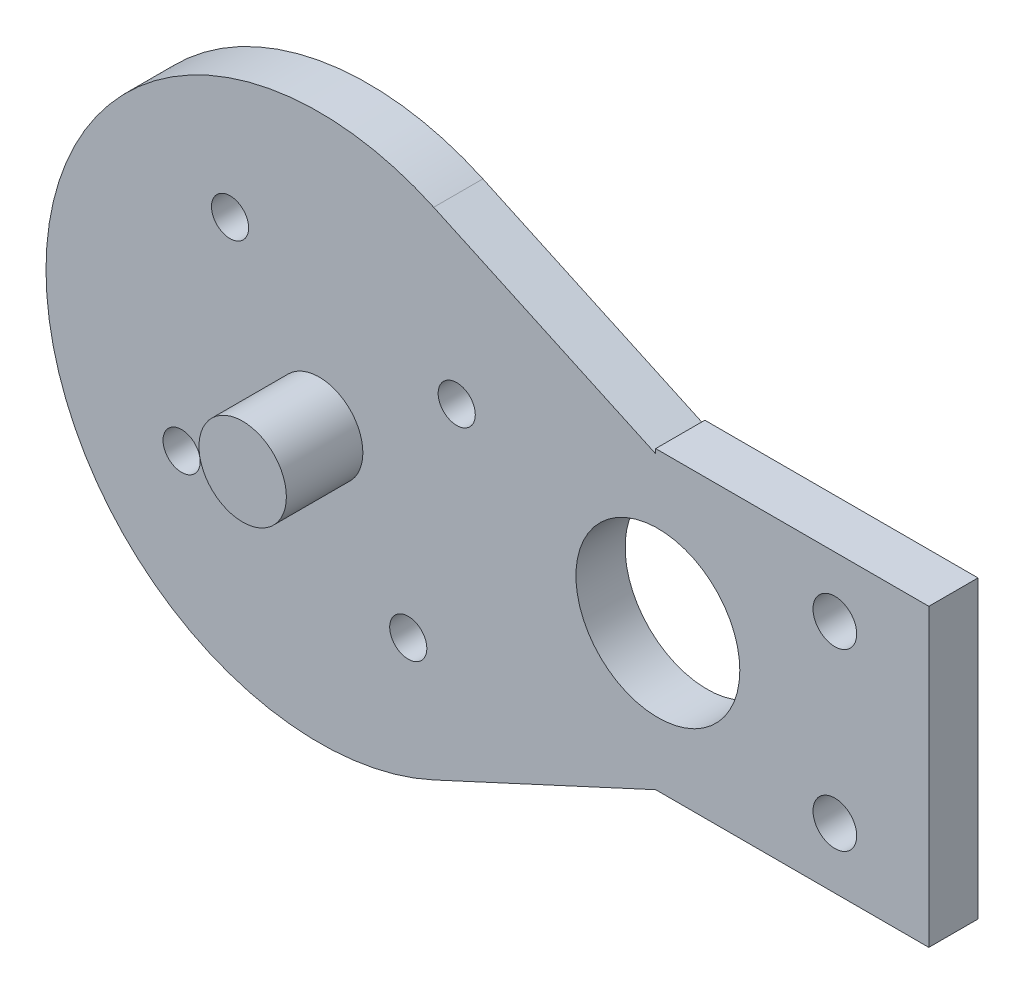
SolidWorks part; units mm, degrees
ref_plane "Front Plane" through (0, 0, 0) normal (0, 0, 1) x (1, 0, 0)
ref_plane "Top Plane" through (0, 0, 0) normal (0, 1, 0) x (1, 0, 0)
ref_plane "Right Plane" through (0, 0, 0) normal (1, 0, 0) x (0, 0, -1)
sketch "Sketch1" plane through (0, 0, 0) normal (0, 0, 1) x (1, 0, 0)
  line L0 (10.4839, 22.6956) -> (36.0323, 10.8939)
  line L1 (36.0323, -10.8939) -> (10.4839, -22.6956)
  circle A0 centre (0, 0) radius 22.215 construction
  circle A1 centre (31, 0) radius 10.2 construction
  arc A2 (10.4839, 22.6956) -> (10.4839, -22.6956) centre (0, 0) ccw
  arc A3 (36.0323, -10.8939) -> (36.0323, 10.8939) centre (31, 0) ccw
  dimension "D1" = 20.4
  dimension "D2" = 44.43
  dimension "D4" = 25
  dimension "D5" = 12
  dimension "D3" = 31
extrude "Boss-Extrude1" add sketch "Sketch1" along normal blind 4.5
sketch "Sketch2" plane through (0, 0, 4.5) normal (0, 0, 1) x (1, 0, 0)
  circle A0 centre (31, 0) radius 7.5
  dimension "D1" = 15
extrude "Cut-Extrude1" cut sketch "Sketch2" against normal through all
sketch "Sketch3" plane through (0, 0, 4.5) normal (0, 0, 1) x (1, 0, 0)
  circle A0 centre (0, 0) radius 4
  dimension "D1" = 8
extrude "Boss-Extrude2" add sketch "Sketch3" along normal blind 7
sketch "Sketch4" plane through (0, 0, 0) normal (0, 0, -1) x (-1, 0, 0)
  line L0 (-36.0323, 10.8939) -> (-56.0323, 10.8939)
  line L1 (-36.0323, -10.8939) -> (-56.0323, -10.8939)
  line L2 (-56.0323, -10.8939) -> (-56.0323, 10.8939)
  line L3 (22.5016, 10.8939) -> (42.5016, 10.8939)
  line L4 (42.5016, 10.8939) -> (42.5016, -10.8939)
  line L5 (42.5016, -10.8939) -> (22.5016, -10.8939)
  arc A0 (-10.4839, -22.6956) -> (-10.4839, 22.6956) centre (0, 0) ccw construction
  arc A1 (22.5016, -10.8939) -> (22.5016, 10.8939) centre (0, 0) ccw
  arc A2 (-36.0323, 10.8939) -> (-36.0323, -10.8939) centre (-31, 0) ccw construction
  arc A3 (-36.0323, 10.8939) -> (-36.0323, -10.8939) centre (-31, 0) ccw
  dimension "D1" = 20
  dimension "D2" = 20
extrude "Boss-Extrude3" add sketch "Sketch4" against normal up to surface (4.5 mm away) up to face at (4, 0, 4.5)
fillet "Fillet1" radius 10 4 edges at (-42.5016, 10.8939, 2.25) (-42.5016, -10.8939, 2.25) (56.0323, -10.8939, 2.25) (56.0323, 10.8939, 2.25)
sketch "Sketch8" plane through (0, 0, 4.5) normal (0, 0, 1) x (1, 0, 0)
  line L0 (56.0323, 0.8939) -> (56.0323, -0.8939) construction
  line L2 (56.0323, 0.8939) -> (56.0323, -0.8939)
  line L3 (55.4014, -4.3896) -> (55.4014, 4.3896)
  line L4 (-42.5016, -0.8939) -> (-42.5016, 0.8939) construction
  line L6 (-42.5016, -0.8939) -> (-42.5016, 0.8939)
  line L7 (-41.8707, 4.3896) -> (-41.8707, -4.3896)
  arc A0 (56.0323, 0.8939) -> (46.0323, 10.8939) centre (46.0323, 0.8939) ccw construction
  arc A1 (46.0323, -10.8939) -> (56.0323, -0.8939) centre (46.0323, -0.8939) ccw construction
  arc A2 (56.0323, 0.8939) -> (55.4014, 4.3896) centre (46.0323, 0.8939) ccw
  arc A3 (55.4014, -4.3896) -> (56.0323, -0.8939) centre (46.0323, -0.8939) ccw
  arc A4 (-32.5016, 10.8939) -> (-42.5016, 0.8939) centre (-32.5016, 0.8939) ccw construction
  arc A5 (-42.5016, -0.8939) -> (-32.5016, -10.8939) centre (-32.5016, -0.8939) ccw construction
  arc A6 (-41.8707, 4.3896) -> (-42.5016, 0.8939) centre (-32.5016, 0.8939) ccw
  arc A7 (-42.5016, -0.8939) -> (-41.8707, -4.3896) centre (-32.5016, -0.8939) ccw
extrude "Cut-Extrude4" cut sketch "Sketch8" against normal through all
sketch "Sketch9" plane through (0, 0, 4.5) normal (0, 0, 1) x (1, 0, 0)
  circle A0 centre (0, 0) radius 15 construction
  circle A1 centre (-8.1543, 12.59) radius 1
  circle A2 centre (12.59, 8.1543) radius 1
  circle A3 centre (8.1543, -12.59) radius 1
  circle A4 centre (-12.59, -8.1543) radius 1
  point P14 (0, 0)
  dimension "D1" = 30
  dimension "D2" = 2
  dimension "D3" = 4
extrude "Cut-Extrude5" cut sketch "Sketch9" against normal through all
sketch "Sketch10" plane through (0, 0, 4.5) normal (0, 0, 1) x (1, 0, 0)
  circle A0 centre (-8.1543, 12.59) radius 1.7
  circle A1 centre (12.59, 8.1543) radius 1.7
  circle A2 centre (8.1543, -12.59) radius 1.7
  circle A3 centre (-12.59, -8.1543) radius 1.7
  dimension "D1" = 3.4
extrude "Cut-Extrude6" cut sketch "Sketch10" against normal blind 2.4
sketch "Sketch11" plane through (0, 0, 0) normal (0, 0, -1) x (-1, 0, 0)
  line L0 (-40.9602, 14.6461) -> (-73.6718, 18.9155)
  line L1 (-73.6718, 18.9155) -> (-68.6403, -15.6759)
  line L2 (-68.6403, -15.6759) -> (-41.445, -13.2122)
  arc A0 (-40.9602, 14.6461) -> (-41.445, -13.2122) centre (0, 0) ccw
  dimension "D1" = 87
extrude "Cut-Extrude7" cut sketch "Sketch11" against normal up to surface (4.5 mm away) up to face at (-6.4543, 12.59, 4.5)
fillet "Fillet2" radius 10 2 edges at (42.1138, -10.8939, 2.25) (42.1138, 10.8939, 2.25)
sketch "Sketch12" plane through (0, 0, 4.5) normal (0, 0, 1) x (1, 0, 0)
  line L0 (-22.5016, 10.8939) -> (-42.5927, 14.8195)
  line L1 (-42.5927, 14.8195) -> (-48.1481, -13.6126)
  line L2 (-48.1481, -13.6126) -> (-27.4273, -14.3153)
  line L3 (-27.4273, -14.3153) -> (-22.5016, -10.8939)
  arc A0 (-22.5016, 10.8939) -> (-22.5016, -10.8939) centre (0, 0) ccw
extrude "Cut-Extrude8" cut sketch "Sketch12" against normal through all
sketch "Sketch20" plane through (0, 0, 4.5) normal (0, 0, 1) x (1, 0, 0)
  line L0 (10.4839, -22.6956) -> (36.0323, -10.8939) construction
  line L1 (55.7986, 13.7261) -> (30.7986, 13.7261)
  line L3 (55.7986, -13.3115) -> (30.7986, -13.3115)
  line L4 (30.7986, 13.7261) -> (30.7986, 7.4973)
  line L5 (35, -13.2734) -> (30.7986, -13.3115) construction
  line L6 (55.7986, 13.7261) -> (55.7986, -13.3115)
  line L7 (30.7986, -7.4973) -> (30.7986, -13.3115)
  circle A0 centre (31, 0) radius 7.5 construction
  circle A1 centre (31, 0) radius 7.5
  circle A2 centre (47.1978, -7.7736) radius 1 construction
  circle A3 centre (47.1978, 8.2264) radius 1 construction
  circle A4 centre (47.1978, -7.7736) radius 1
  circle A5 centre (47.1978, 8.2264) radius 1
  line M7 (10.4839, -22.6956) -> (36.0323, -10.8939)
  arc M8 (36.0323, -10.8939) -> (43.4709, -1.5916) centre (33.4776, -1.2257) ccw
  arc M9 (43.4709, -1.5916) -> (43.4709, 1.5916) centre (0, 0) ccw
  arc M10 (43.4709, 1.5916) -> (36.0323, 10.8939) centre (33.4776, 1.2257) ccw
  line M11 (36.0323, 10.8939) -> (10.4839, 22.6956)
  dimension "D1" = 25
extrude "Boss-Extrude4" add sketch "Sketch20" against normal up to surface (4.5 mm away) contours L6 L1 L4 L3 A5 A4 M11 M10 M9 M8 M7 region at (47.4771, 0.3317, 4.5) up to face at (-7.1543, 12.59, 0)
sketch "Sketch21" plane through (0, 0, 4.5) normal (0, 0, 1) x (1, 0, 0)
  circle A0 centre (47.1978, 8.2264) radius 2
  circle A1 centre (47.1978, -7.7736) radius 2
  dimension "D1" = 4
extrude "Cut-Extrude9" cut sketch "Sketch21" against normal blind 3
